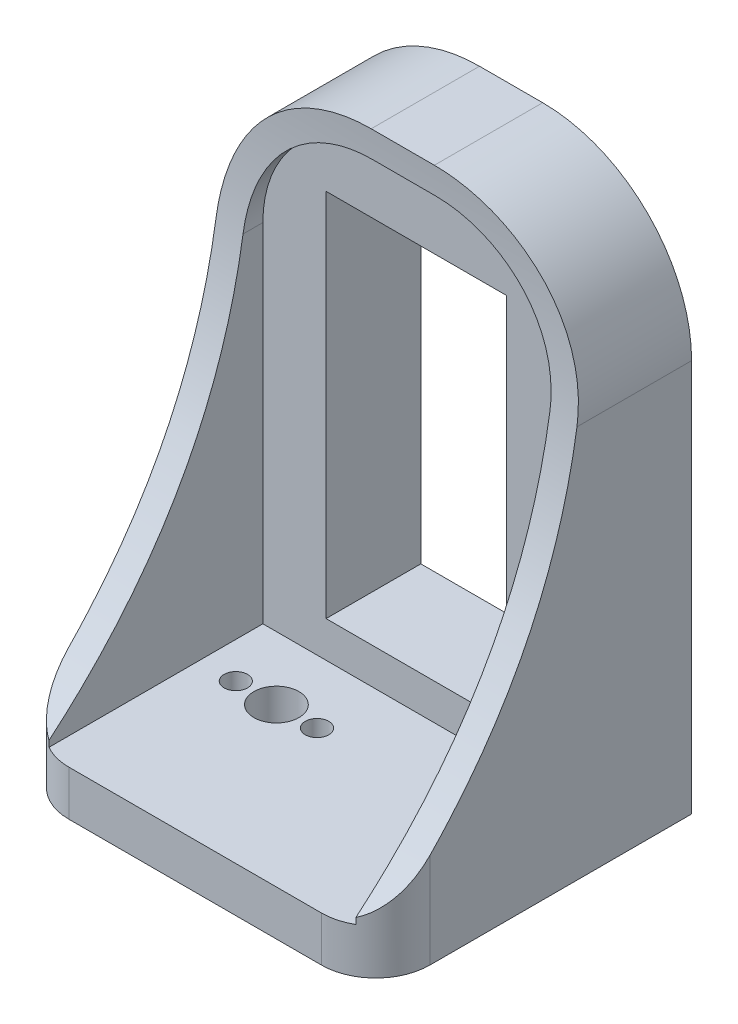
SolidWorks part; units mm, degrees
ref_plane "Front Plane" through (0, 0, 0) normal (0, 0, 1) x (1, 0, 0)
ref_plane "Top Plane" through (0, 0, 0) normal (0, 1, 0) x (1, 0, 0)
ref_plane "Right Plane" through (0, 0, 0) normal (1, 0, 0) x (0, 0, -1)
sketch "Sketch1" plane through (0, 0, 0) normal (0, 1, 0) x (1, 0, 0)
  line L1 (-20, 17.5) -> (20, 17.5)
  line L2 (-20, 17.5) -> (-20, -17.5)
  line L3 (-20, -17.5) -> (20, -17.5)
  line L4 (20, 17.5) -> (20, -17.5)
  line L5 (-20, 17.5) -> (20, -17.5) construction
  line L6 (-20, -17.5) -> (20, 17.5) construction
  point P0 (0, 0)
  dimension "D1" = 35
  dimension "D2" = 40
extrude "Boss-Extrude1" add sketch "Sketch1" along normal blind 60
sketch "Sketch2" plane through (20, 0, 0) normal (1, 0, 0) x (0, 0, -1)
  line L0 (-17.5, 0) -> (17.5, 0) construction
  line L1 (-17.5, 60) -> (7, 60)
  line L2 (-17.5, 60) -> (-17.5, 5)
  line L3 (-17.5, 5) -> (7, 5)
  line L4 (7, 60) -> (7, 5)
  line L5 (17.5, 60) -> (17.5, 0) construction
  dimension "D1" = 5
  dimension "D2" = 10.5
extrude "Cut-Extrude1" cut sketch "Sketch2" against normal blind 46
sketch "Sketch3" plane through (20, 0, 0) normal (1, 0, 0) x (0, 0, -1)
  line L0 (7, 60) -> (5.5, 60)
  line L1 (-17.5, 5) -> (7, 5) construction
  line L2 (7, 5) -> (7, 60) construction
  line L3 (-17.5, 5) -> (7, 5)
  line L4 (7, 5) -> (7, 60)
  spline S0 degree 2 poles (5.5, 60) (7.5181, 25.4967) (-17.5, 5) knots 0 0 0 1 1 1
  dimension "D1" = 1.5
extrude "Boss-Extrude2" add sketch "Sketch3" against normal blind 3
mirror "Mirror1" about plane through (0, 0, 0) normal (1, 0, 0) of "Boss-Extrude2"
sketch "Sketch4" plane through (17, 0, 0) normal (-1, 0, 0) x (0, 0, 1)
  line L0 (-7, 57) -> (-5.625, 57)
  line L3 (-7, 60) -> (-7, 5)
  line L4 (-7, 5) -> (17.5, 5)
  line L5 (-5.5, 60) -> (-7, 60)
  line L6 (-7, 60) -> (-7, 5)
  line L7 (-7, 5) -> (17.5, 5)
  line L8 (-5.5, 60) -> (-7, 60)
  parabola Q1 (17.5, 5) -> (-5.5, 60) focus (26.9928, 38.0156) apex (1.2568, 24.6826)
  parabola Q2 (17.5, 5) -> (-5.5, 60) focus (26.9928, 38.0156) apex (1.2568, 24.6826)
  line M6 (-7, 60) -> (-7, 5)
  spline M8 degree 2 poles (-5.5, 60) (-7.5181, 25.4967) (17.5, 5) knots 0 0 0 1 1 1
  line M9 (-5.5, 60) -> (-7, 60)
  dimension "D2" = 3
  dimension "D1" = 0
extrude "Boss-Extrude3" add sketch "Sketch4" along normal up to surface (34 mm away) contours L0 M6 M8 M9 region at (17, 58.5219, -6.285) up to face at (-17, 39.375, -0.3125)
fillet "Fillet1" radius 13.5 2 edges
fillet "Fillet2" radius 16.5 2 edges at (20, 60, -11.5) (-20, 60, -11.5)
fillet "Fillet3" radius 6 2 edges at (-20, 2.5, 17.5) (20, 2.5, 17.5)
sketch "Sketch5" plane through (0, 0, -7) normal (0, 0, 1) x (1, 0, 0)
  line L0 (-17, 5) -> (17, 5) construction
  line L1 (-10, 50) -> (10, 50)
  line L2 (-10, 50) -> (-10, 9)
  line L3 (-10, 9) -> (10, 9)
  line L4 (10, 50) -> (10, 9)
  line L5 (-10, 50) -> (10, 9) construction
  line L6 (-10, 9) -> (10, 50) construction
  point P0 (0, 29.5)
  dimension "D1" = 20
  dimension "D2" = 41
  dimension "D3" = 4
extrude "Cut-Extrude2" cut sketch "Sketch5" against normal through all
sketch "Sketch8" plane through (0, 5, 0) normal (0, 1, 0) x (1, 0, 0)
  line L0 (-20, 4.8002) -> (-20, 17.5) construction
  circle A0 centre (-4, 0) radius 1.3
  circle A1 centre (-8.5, 0) radius 2.5
  circle A2 centre (-13, 0) radius 1.3
  dimension "D1" = 2.6
  dimension "D2" = 5
  dimension "D3" = 4.5
  dimension "D4" = 9
  dimension "D5" = 11.5
extrude "Cut-Extrude5" cut sketch "Sketch8" against normal through all
scale "Scale1" [suppressed]
sketch "Sketch9" plane through (0, 0, -17.5) normal (0, 0, -1) x (-1, 0, 0)
  line L0 (-5, 54.45) -> (5, 54.45) construction
  line L1 (5, 4.55) -> (-5, 4.55) construction
  line L2 (-10, 50) -> (10, 50) construction
  line L3 (10, 9) -> (-10, 9) construction
  circle A0 centre (-5, 54.45) radius 2.15
  circle A1 centre (5, 54.45) radius 2.15
  circle A2 centre (5, 4.55) radius 2.15
  circle A3 centre (-5, 4.55) radius 2.15
  point P12 (0, 54.45)
  point P13 (0, 50)
  point P14 (0, 4.55)
  dimension "D4" = 4.3
  dimension "D1" = 4.45
  dimension "D2" = 4.45
  dimension "D3" = 10
extrude "Cut-Extrude6" cut sketch "Sketch9" against normal blind 10
